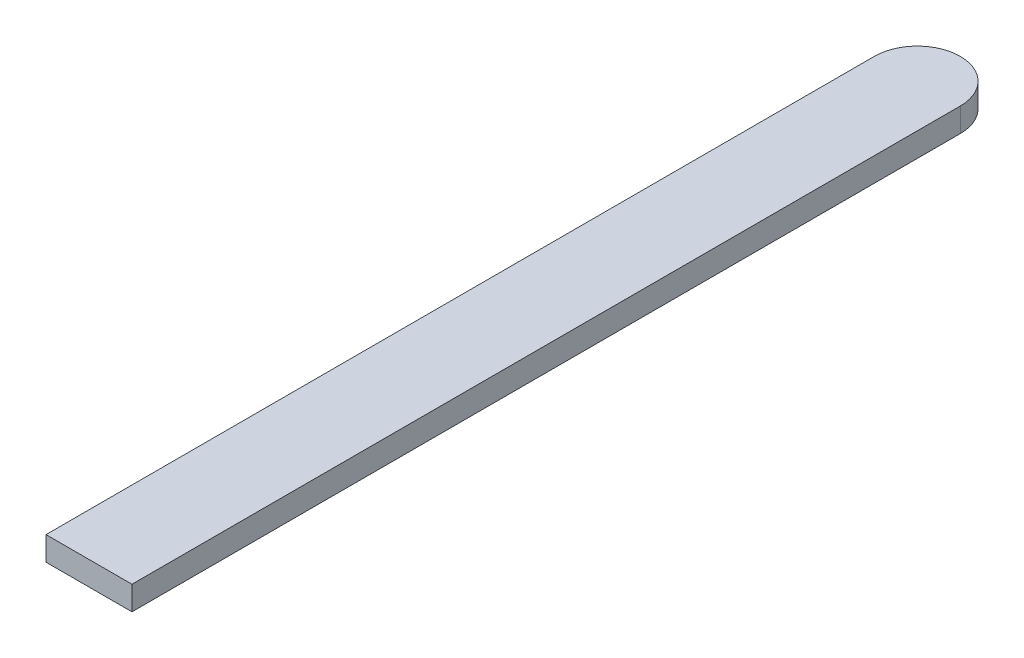
SolidWorks part; units mm, degrees
ref_plane "Front Plane" through (0, 0, 0) normal (0, 0, 1) x (1, 0, 0)
ref_plane "Top Plane" through (0, 0, 0) normal (0, 1, 0) x (1, 0, 0)
ref_plane "Right Plane" through (0, 0, 0) normal (1, 0, 0) x (0, 0, -1)
sketch "Sketch1" plane through (0, 0, 0) normal (0, 1, 0) x (1, 0, 0)
  line L0 (0, 0) -> (0, 35.2425) construction
  line L1 (-2.875, 0) -> (-2.875, 35.2425)
  line L2 (2.875, 0) -> (2.875, 35.2425)
  line L3 (-2.875, 0) -> (2.875, 0)
  line L6 (2.875, 0) -> (-2.875, 0)
  line L7 (2.875, 0) -> (2.875, -20.1575)
  line L8 (2.875, -20.1575) -> (-2.875, -20.1575)
  line L9 (-2.875, 0) -> (-2.875, -20.1575)
  line L10 (-10.6594, -20.1575) -> (-7.8276, -20.1575) construction
  arc A0 (-2.875, 0) -> (2.875, 0) centre (0, 0) ccw
  arc A1 (2.875, 35.2425) -> (-2.875, 35.2425) centre (0, 35.2425) ccw
  point P3 (0, 17.6212)
  point P10 (0, 38.1175)
  dimension "D1" = 5.75
extrude "Boss-Extrude1" add sketch "Sketch1" along normal blind 1.6 contours L2 A1 L1 L3 | A0 L9 L8 L7 | L3 A0 L6 region at (0, 0, -18.7557) region at (0, 0, 11.1963) region at (0, 0, 1.2202)
ref_axis "Axis1" through (0, 1.6, -35.2425) along (0, -1, 0)
